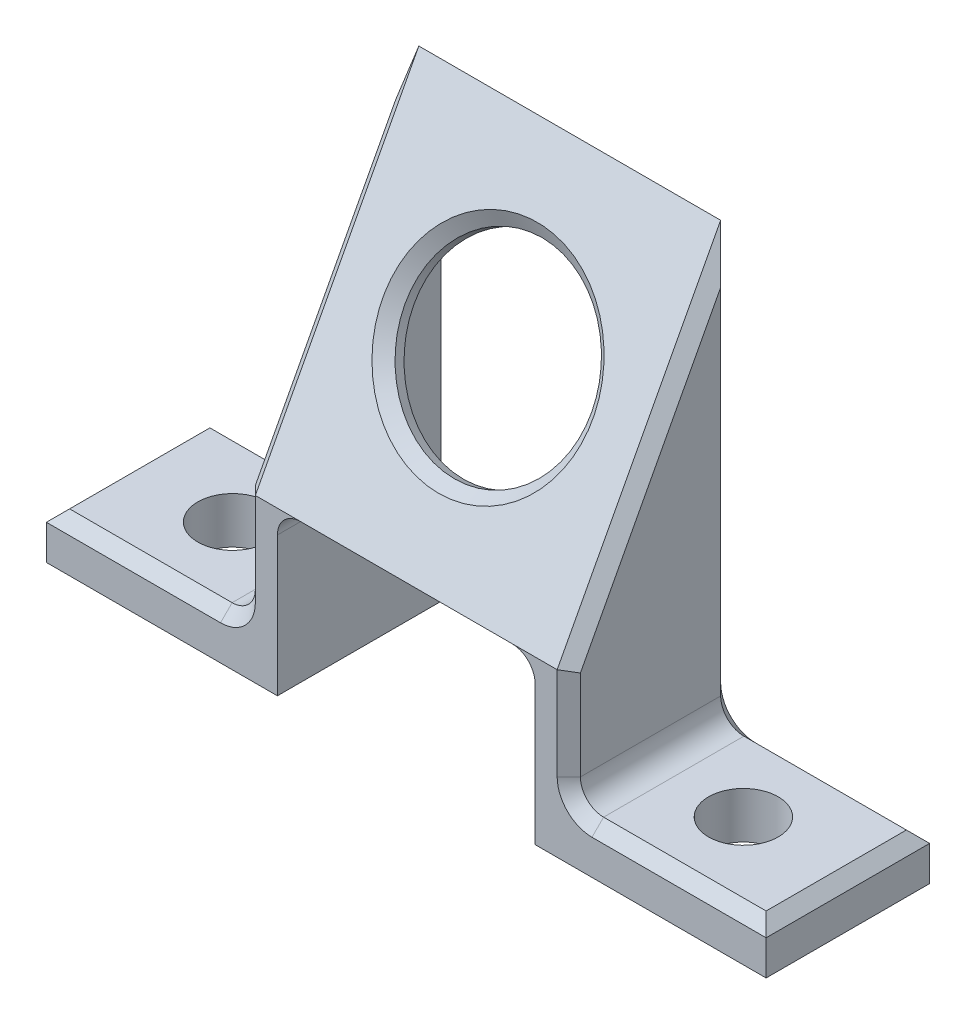
SolidWorks part; units mm, degrees
material "6061-T6 (SS)"
ref_plane "Front Plane" through (0, 0, 0) normal (0, 0, 1) x (1, 0, 0)
ref_plane "Top Plane" through (0, 0, 0) normal (0, 1, 0) x (1, 0, 0)
ref_plane "Right Plane" through (0, 0, 0) normal (1, 0, 0) x (0, 0, -1)
sketch "Sketch1" plane through (0, 0, 0) normal (1, 0, 0) x (0, 0, -1)
  line L0 (0, 0) -> (14.0841, 0)
  line L1 (14.0841, 0) -> (14.0841, 26.4884)
  line L2 (14.0841, 26.4884) -> (0, 0)
  dimension "D1" = 28
  dimension "D2" = 30
extrude "Boss-Extrude1" add sketch "Sketch1" along normal blind 14 and the other way blind 14
sketch "Sketch5" plane through (0, 0, 0) normal (0, 0, 1) x (1, 0, 0)
  line L0 (0, -55) -> (0, 55) construction
  line L1 (14, 0) -> (11.1, 0)
  line L2 (14, 0) -> (14, -14)
  line L3 (14, -14) -> (11.1, -14)
  line L4 (11.1, 0) -> (11.1, -14)
  line L5 (14, -14) -> (31, -14)
  line L6 (14, -14) -> (14, -10)
  line L7 (14, -10) -> (31, -10)
  line L8 (31, -14) -> (31, -10)
  line L9 (-14, -14) -> (-11.1, -14)
  line L10 (-11.1, 0) -> (-11.1, -14)
  line L11 (-14, 0) -> (-11.1, 0)
  line L12 (-14, 0) -> (-14, -14)
  line L13 (-14, -10) -> (-31, -10)
  line L14 (-31, -14) -> (-31, -10)
  line L15 (-14, -14) -> (-31, -14)
  line L16 (-14, -14) -> (-14, -10)
  dimension "D1" = 2.9
  dimension "D2" = 14
  dimension "D3" = 4
  dimension "D4" = 17
extrude "Boss-Extrude3" add sketch "Sketch5" against normal up to surface (14.0841 mm away) contours L5 L8 L7 L2 | L1 L4 L3 L2 | L15 L12 L13 L14 | L9 L10 L11 L12 region at (12.55, -7, 0) region at (22.5, -12, 0) region at (-22.5, -12, 0) up to face at (0, 13.2442, -14.0841)
sketch "Sketch6" plane through (0, 0, 0) normal (1, 0, 0) x (0, 0, -1)
  line L0 (14.0841, 0) -> (2.1268, 0)
  line L1 (2.1268, 0) -> (14.0841, 22.4884)
  line L2 (14.0841, -10) -> (14.0841, 26.4884) construction
  line L3 (14.0841, 22.4884) -> (14.0841, 0)
  dimension "D1" = 28
  dimension "D2" = 4
extrude "Cut-Extrude1" cut sketch "Sketch6" against normal up to surface (11.1 mm away) from surface up to face at (-11.1, -7, -7.0421) starting at face at (11.1, -7, -7.0421)
sketch "Sketch7" plane through (0, 0, 0) normal (0, 0.4695, 0.8829) x (1, 0, 0)
  line L0 (-14, 30) -> (14, 0) construction
  line L1 (14, 0) -> (-14, 0) construction
  line L2 (-14, 0) -> (14, 30) construction
  circle A0 centre (0, 15) radius 8.05
  dimension "D1" = 16.1
extrude "Cut-Extrude2" cut sketch "Sketch7" against normal blind 3
sketch "Sketch8" plane through (0, -10, 0) normal (0, 1, 0) x (1, 0, 0)
  line L0 (14, 14.0841) -> (14, 0) construction
  line L2 (31, 14.0841) -> (31, 0) construction
  line L3 (14, 7.0421) -> (31, 7.0421) construction
  line L4 (0, -7.7463) -> (0, 7.7463) construction
  circle A0 centre (22, 7.0421) radius 5
  circle A1 centre (22, 7.0421) radius 3
  circle A2 centre (-22, 7.0421) radius 5
  circle A3 centre (-22, 7.0421) radius 3
  dimension "D2" = 10
  dimension "D3" = 6
  dimension "D1" = 8
extrude "Cut-Extrude4" cut sketch "Sketch8" against normal through all contours A3 | A1
fillet "Fillet4" radius 2 6 edges at (-14, -10, -7.0421) (14, -10, -7.0421) (11.1, 11.2442, -8.1055) (-11.1, 11.2442, -8.1055) (11.1, 0, -1.0634) (-11.1, 0, -1.0634)
chamfer "Chamfer6" distance 1 angle 45 17 edges at (14, 9.2442, -14.0841) (14.5858, -9.4142, -14.0841) (23.5, -10, -14.0841) (31, -10, -7.0421) (23.5, -10, 0) (14.5858, -9.4142, 0) (14, -4, 0) (14, 13.2442, -7.0421) (0, 6.1365, -3.2628) (-31, -10, -7.0421) (-23.5, -10, -14.0841) (-14.5858, -9.4142, -14.0841) (-14, 9.2442, -14.0841) (-14, 13.2442, -7.0421) (-14, -4, 0) (-14.5858, -9.4142, 0) (-23.5, -10, 0)
